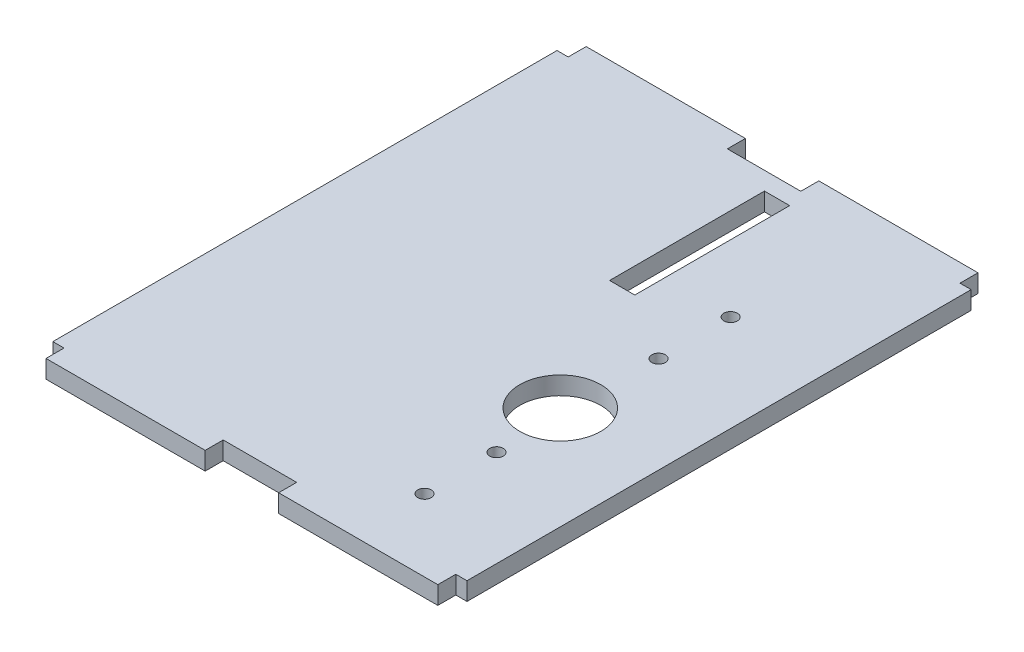
SolidWorks part; units mm, degrees
ref_plane "Front Plane" through (0, 0, 0) normal (0, 0, 1) x (1, 0, 0)
ref_plane "Top Plane" through (0, 0, 0) normal (0, 1, 0) x (1, 0, 0)
ref_plane "Right Plane" through (0, 0, 0) normal (1, 0, 0) x (0, 0, -1)
sketch "Sketch1" plane through (0, 0, 0) normal (0, 1, 0) x (1, 0, 0)
  line L1 (0, 0) -> (292.1, 0)
  line L2 (0, 0) -> (0, 355.6)
  line L3 (0, 355.6) -> (292.1, 355.6)
  line L4 (292.1, 0) -> (292.1, 355.6)
  ellipse E1 centre (219.5122, 138.3861) end of major axis (248.0872, 138.3861) minor radius 28.574
  dimension "D1" = 355.6
  dimension "D2" = 292.1
extrude "Boss-Extrude1" add sketch "Sketch1" along normal blind 12.7
sketch "Sketch2" plane through (0, 0, 0) normal (0, -1, 0) x (1, 0, 0)
  line L0 (0, 0) -> (292.1, 0) construction
  line L1 (0, -355.6) -> (0, 0) construction
  circle A0 centre (224.028, -38.1) radius 4.7625
  circle A1 centre (224.028, -88.9) radius 4.7625
  circle A2 centre (224.028, -203.2) radius 4.7625
  circle A3 centre (224.028, -254) radius 4.7625
  dimension "D3" = 88.9
  dimension "D6" = 9.525
  dimension "D1" = 38.1
  dimension "D2" = 224.028
  dimension "D4" = 203.2
  dimension "D5" = 254
  dimension "D7" = 224.028
  dimension "D8" = 224.028
  dimension "D9" = 224.028
extrude "Cut-Extrude1" cut sketch "Sketch2" against normal blind 12.7
sketch "Sketch3" plane through (0, 12.7, 0) normal (0, 1, 0) x (1, 0, 0)
  line L0 (146.05, 355.6) -> (146.05, 250.206) construction
  line L1 (0, 177.8) -> (22.2548, 177.8) construction
  line L2 (7.874, 355.6) -> (120.142, 355.6)
  line L3 (7.874, 355.6) -> (7.874, 368.3)
  line L4 (0, 355.6) -> (0, 0)
  line L5 (0, 0) -> (292.1, 0)
  line L6 (292.1, 0) -> (292.1, 355.6)
  line L7 (292.1, 355.6) -> (0, 355.6)
  line L8 (0, 355.6) -> (0, 0) construction
  line L9 (0, 0) -> (292.1, 0) construction
  line L10 (292.1, 0) -> (292.1, 355.6) construction
  line L11 (292.1, 355.6) -> (0, 355.6) construction
  line L12 (7.874, 368.3) -> (120.142, 368.3)
  line L13 (120.142, 355.6) -> (120.142, 368.3)
  line L14 (284.226, 368.3) -> (171.958, 368.3)
  line L15 (171.958, 355.6) -> (171.958, 368.3)
  line L16 (284.226, 355.6) -> (171.958, 355.6)
  line L17 (284.226, 355.6) -> (284.226, 368.3)
  line L18 (284.226, 0) -> (284.226, -12.7)
  line L19 (284.226, 0) -> (171.958, 0)
  line L20 (171.958, 0) -> (171.958, -12.7)
  line L21 (284.226, -12.7) -> (171.958, -12.7)
  line L22 (7.874, -12.7) -> (120.142, -12.7)
  line L23 (120.142, 0) -> (120.142, -12.7)
  line L24 (7.874, 0) -> (120.142, 0)
  line L25 (7.874, 0) -> (7.874, -12.7)
  dimension "D2" = 25.908
  dimension "D3" = 112.268
  dimension "D4" = 12.7
  dimension "D1" = 0
extrude "Boss-Extrude2" add sketch "Sketch3" against normal blind 12.7
sketch "Sketch4" plane through (0, 0, 0) normal (0, -1, 0) x (1, 0, 0)
  line L20 (0, 0) -> (0, -355.6)
  line L21 (0, -355.6) -> (7.874, -355.6)
  line L22 (7.874, -355.6) -> (7.874, -368.3)
  line L23 (7.874, -368.3) -> (120.142, -368.3)
  line L24 (120.142, -368.3) -> (120.142, -355.6)
  line L25 (120.142, -355.6) -> (171.958, -355.6)
  line L26 (171.958, -355.6) -> (171.958, -368.3)
  line L27 (171.958, -368.3) -> (284.226, -368.3)
  line L28 (284.226, -368.3) -> (284.226, -355.6)
  line L29 (284.226, -355.6) -> (292.1, -355.6)
  line L30 (292.1, -355.6) -> (292.1, 0)
  line L31 (292.1, 0) -> (284.226, 0)
  line L32 (284.226, 0) -> (284.226, 12.7)
  line L33 (284.226, 12.7) -> (171.958, 12.7)
  line L34 (171.958, 12.7) -> (171.958, 0)
  line L35 (171.958, 0) -> (120.142, 0)
  line L36 (120.142, 0) -> (120.142, 12.7)
  line L37 (120.142, 12.7) -> (7.874, 12.7)
  line L38 (7.874, 12.7) -> (7.874, 0)
  line L39 (7.874, 0) -> (0, 0)
  line L40 (0, 0) -> (0, -355.6)
  line L41 (0, -355.6) -> (7.874, -355.6)
  line L42 (7.874, -355.6) -> (7.874, -368.3)
  line L43 (7.874, -368.3) -> (120.142, -368.3)
  line L44 (120.142, -368.3) -> (120.142, -355.6)
  line L45 (120.142, -355.6) -> (171.958, -355.6)
  line L46 (171.958, -355.6) -> (171.958, -368.3)
  line L47 (171.958, -368.3) -> (284.226, -368.3)
  line L48 (284.226, -368.3) -> (284.226, -355.6)
  line L49 (284.226, -355.6) -> (292.1, -355.6)
  line L50 (292.1, -355.6) -> (292.1, 0)
  line L51 (292.1, 0) -> (284.226, 0)
  line L52 (284.226, 0) -> (284.226, 12.7)
  line L53 (284.226, 12.7) -> (171.958, 12.7)
  line L54 (171.958, 12.7) -> (171.958, 0)
  line L55 (171.958, 0) -> (120.142, 0)
  line L56 (120.142, 0) -> (120.142, 12.7)
  line L57 (120.142, 12.7) -> (7.874, 12.7)
  line L58 (7.874, 12.7) -> (7.874, 0)
  line L59 (7.874, 0) -> (0, 0)
  circle A5 centre (224.028, -203.2) radius 4.7625 construction
  circle A6 centre (224.028, -88.9) radius 4.7625 construction
  dimension "D3" = 109.5375
  dimension "D1" = 0
sketch "Sketch5" plane through (0, 12.7, 0) normal (0, 1, 0) x (1, 0, 0)
  line L0 (171.958, 368.3) -> (284.226, 368.3) construction
  line L2 (292.1, 355.6) -> (292.1, 0) construction
  line L4 (120.142, 355.6) -> (171.958, 355.6) construction
  line L5 (176.784, 342.9) -> (159.004, 342.9)
  line L6 (176.784, 342.9) -> (176.784, 233.68)
  line L7 (176.784, 233.68) -> (159.004, 233.68)
  line L8 (159.004, 342.9) -> (159.004, 233.68)
  point P10 (176.784, 342.9)
  dimension "D1" = 25.4
  dimension "D2" = 115.316
  dimension "D3" = 17.78
  dimension "D4" = 109.22
extrude "Cut-Extrude2" cut sketch "Sketch5" against normal through all
